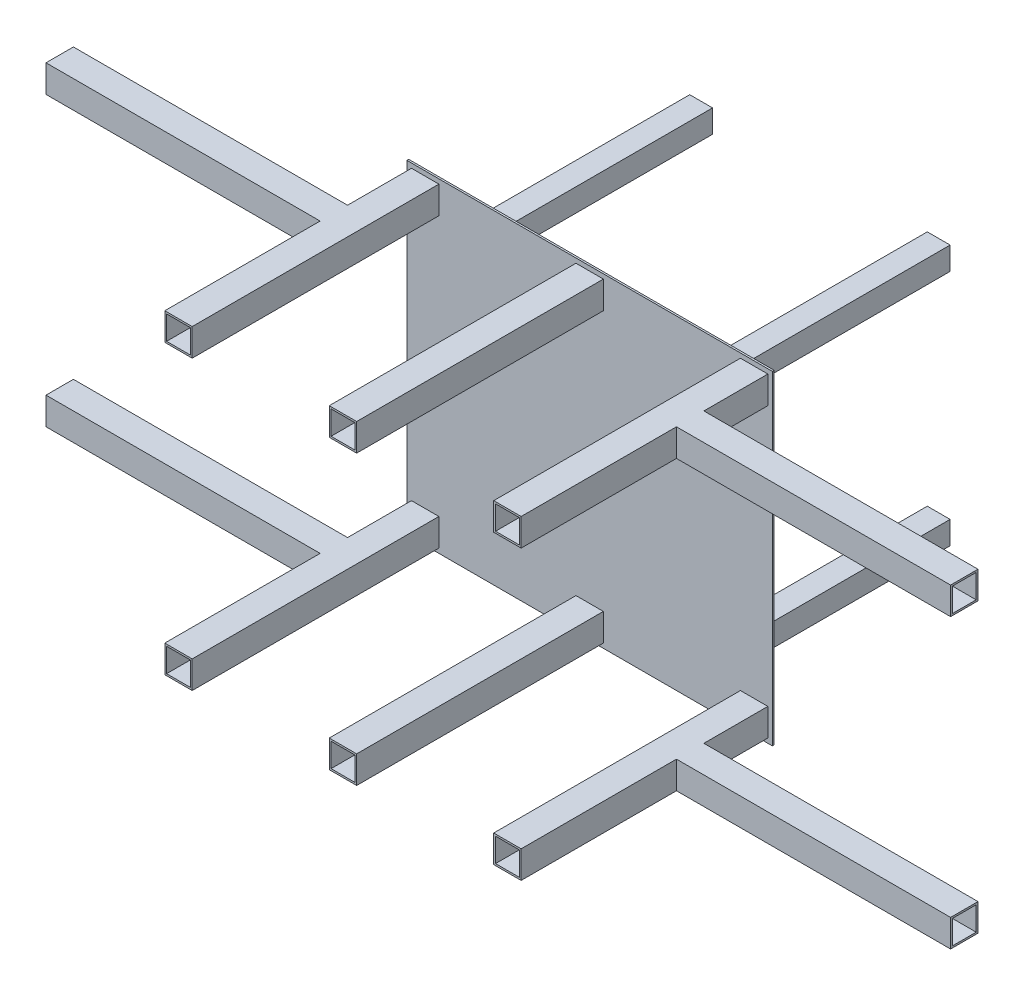
SolidWorks part; units mm, degrees
ref_plane "前基準面" through (0, 0, 0) normal (0, 0, 1) x (1, 0, 0)
ref_plane "上基準面" through (0, 0, 0) normal (0, 1, 0) x (1, 0, 0)
ref_plane "右基準面" through (0, 0, 0) normal (1, 0, 0) x (0, 0, -1)
sketch "草圖1" plane through (0, 0, 0) normal (0, 0, 1) x (1, 0, 0)
  line L0 (27.1343, 30.6601) -> (53.1343, 30.6601)
  line L1 (-159.8657, 37.6601) -> (240.1343, 37.6601)
  line L2 (-159.8657, 37.6601) -> (-159.8657, -317.3399)
  line L3 (-159.8657, -317.3399) -> (240.1343, -317.3399)
  line L4 (240.1343, 37.6601) -> (240.1343, -317.3399)
  line L5 (-152.8657, 30.6601) -> (-126.8657, 30.6601)
  line L6 (-152.8657, 30.6601) -> (-152.8657, 4.6601)
  line L7 (-152.8657, 4.6601) -> (-126.8657, 4.6601)
  line L8 (-126.8657, 30.6601) -> (-126.8657, 4.6601)
  line L9 (-154.8657, 32.6601) -> (-124.8657, 32.6601)
  line L10 (-154.8657, 32.6601) -> (-154.8657, 2.6601)
  line L11 (-154.8657, 2.6601) -> (-124.8657, 2.6601)
  line L12 (-124.8657, 32.6601) -> (-124.8657, 2.6601)
  line L13 (25.1343, 32.6601) -> (55.1343, 32.6601)
  line L14 (25.1343, 32.6601) -> (25.1343, 2.6601)
  line L15 (25.1343, 2.6601) -> (55.1343, 2.6601)
  line L16 (55.1343, 32.6601) -> (55.1343, 2.6601)
  line L17 (53.1343, 30.6601) -> (53.1343, 4.6601)
  line L18 (27.1343, 4.6601) -> (53.1343, 4.6601)
  line L19 (27.1343, 30.6601) -> (27.1343, 4.6601)
  line L20 (207.1343, 4.6601) -> (233.1343, 4.6601)
  line L21 (205.1343, 32.6601) -> (235.1343, 32.6601)
  line L22 (205.1343, 32.6601) -> (205.1343, 2.6601)
  line L23 (205.1343, 2.6601) -> (235.1343, 2.6601)
  line L24 (235.1343, 32.6601) -> (235.1343, 2.6601)
  line L25 (233.1343, 30.6601) -> (233.1343, 4.6601)
  line L26 (207.1343, 30.6601) -> (233.1343, 30.6601)
  line L27 (207.1343, 30.6601) -> (207.1343, 4.6601)
  line L28 (-152.8657, -284.3399) -> (-126.8657, -284.3399)
  line L29 (-154.8657, -282.3399) -> (-124.8657, -282.3399)
  line L30 (-154.8657, -282.3399) -> (-154.8657, -312.3399)
  line L31 (-154.8657, -312.3399) -> (-124.8657, -312.3399)
  line L32 (-124.8657, -282.3399) -> (-124.8657, -312.3399)
  line L33 (25.1343, -282.3399) -> (55.1343, -282.3399)
  line L34 (25.1343, -282.3399) -> (25.1343, -312.3399)
  line L35 (25.1343, -312.3399) -> (55.1343, -312.3399)
  line L36 (55.1343, -282.3399) -> (55.1343, -312.3399)
  line L37 (205.1343, -282.3399) -> (235.1343, -282.3399)
  line L38 (205.1343, -282.3399) -> (205.1343, -312.3399)
  line L39 (205.1343, -312.3399) -> (235.1343, -312.3399)
  line L40 (235.1343, -282.3399) -> (235.1343, -312.3399)
  line L41 (-126.8657, -284.3399) -> (-126.8657, -310.3399)
  line L42 (-152.8657, -310.3399) -> (-126.8657, -310.3399)
  line L43 (-152.8657, -284.3399) -> (-152.8657, -310.3399)
  line L44 (27.1343, -284.3399) -> (53.1343, -284.3399)
  line L45 (53.1343, -284.3399) -> (53.1343, -310.3399)
  line L46 (27.1343, -310.3399) -> (53.1343, -310.3399)
  line L47 (27.1343, -284.3399) -> (27.1343, -310.3399)
  line L48 (207.1343, -284.3399) -> (233.1343, -284.3399)
  line L49 (233.1343, -284.3399) -> (233.1343, -310.3399)
  line L50 (207.1343, -310.3399) -> (233.1343, -310.3399)
  line L51 (207.1343, -284.3399) -> (207.1343, -310.3399)
  point P52 (-139.8657, -312.3399)
  dimension "D1" = 400
  dimension "D2" = 355
  dimension "D3" = 30
  dimension "D4" = 30
  dimension "D5" = 26
  dimension "D6" = 26
  dimension "D7" = 2
  dimension "D8" = 2
  dimension "D9" = 30
  dimension "D10" = 30
  dimension "D12" = 30
  dimension "D13" = 30
  dimension "D15" = 150
  dimension "D16" = 150
  dimension "D17" = 5
  dimension "D18" = 0
  dimension "D19" = 0
  dimension "D20" = 30
  dimension "D21" = 30
  dimension "D23" = 30
  dimension "D24" = 30
  dimension "D26" = 30
  dimension "D27" = 30
  dimension "D29" = 285
  dimension "D30" = 0
  dimension "D31" = 0
  dimension "D32" = 5
  dimension "D33" = 150
  dimension "D34" = 150
  dimension "D35" = 0
  dimension "D11" = 2
  dimension "D14" = 2
  dimension "D22" = 2
  dimension "D25" = 2
  dimension "D28" = 2
extrude "填料-伸長1" add sketch "草圖1" along normal blind 270 contours L32 L31 L30 L29 | L42 L41 L28 L43 | L35 L36 L33 L34 | L46 L45 L44 L47 | L50 L49 L48 L51 | L39 L40 L37 L38 | L23 L24 L21 L22 | L20 L25 L26 L27 | L15 L16 L13 L14 | L18 L17 L0 L19 | L11 L12 L9 L10 | L7 L8 L5 L6
extrude "填料-伸長2" add sketch "草圖1<4>" against normal blind 2 contours L4 L3 L2 L1
sketch "草圖1<4>" plane through (0, 0, 0) normal (0, 0, 1) x (1, 0, 0) same geometry as "草圖1"
sketch "草圖3" plane through (0, 0, -2) normal (0, 0, -1) x (-1, 0, 0)
  line L0 (-181.1343, 1.1601) -> (-159.1343, 1.1601)
  line L1 (-182.6343, 2.6601) -> (-157.6343, 2.6601)
  line L2 (-182.6343, 2.6601) -> (-182.6343, -22.3399)
  line L3 (-182.6343, -22.3399) -> (-157.6343, -22.3399)
  line L4 (-157.6343, 2.6601) -> (-157.6343, -22.3399)
  line L5 (-159.1343, 1.1601) -> (-159.1343, -20.8399)
  line L6 (-181.1343, -20.8399) -> (-159.1343, -20.8399)
  line L7 (-181.1343, 1.1601) -> (-181.1343, -20.8399)
  line L9 (-240.1343, 37.6601) -> (-240.1343, -317.3399) construction
  line L10 (159.8657, 37.6601) -> (-240.1343, 37.6601) construction
  line L11 (-181.1343, -258.8399) -> (-159.1343, -258.8399)
  line L12 (-182.6343, -257.3399) -> (-157.6343, -257.3399)
  line L13 (-182.6343, -257.3399) -> (-182.6343, -282.3399)
  line L14 (-182.6343, -282.3399) -> (-157.6343, -282.3399)
  line L15 (-157.6343, -257.3399) -> (-157.6343, -282.3399)
  line L16 (-159.1343, -258.8399) -> (-159.1343, -280.8399)
  line L17 (-181.1343, -280.8399) -> (-159.1343, -280.8399)
  line L18 (-181.1343, -258.8399) -> (-181.1343, -280.8399)
  line L19 (159.8657, -317.3399) -> (-240.1343, -317.3399) construction
  line L20 (-40.1343, 37.6601) -> (-40.1343, -317.3399) construction
  line L21 (100.8657, -258.8399) -> (100.8657, -280.8399)
  line L22 (100.8657, -280.8399) -> (78.8657, -280.8399)
  line L23 (78.8657, -258.8399) -> (78.8657, -280.8399)
  line L24 (77.3657, -257.3399) -> (77.3657, -282.3399)
  line L25 (102.3657, -282.3399) -> (77.3657, -282.3399)
  line L26 (102.3657, -257.3399) -> (102.3657, -282.3399)
  line L27 (102.3657, -257.3399) -> (77.3657, -257.3399)
  line L28 (100.8657, -258.8399) -> (78.8657, -258.8399)
  line L29 (100.8657, 1.1601) -> (100.8657, -20.8399)
  line L30 (100.8657, -20.8399) -> (78.8657, -20.8399)
  line L31 (78.8657, 1.1601) -> (78.8657, -20.8399)
  line L32 (77.3657, 2.6601) -> (77.3657, -22.3399)
  line L33 (102.3657, -22.3399) -> (77.3657, -22.3399)
  line L34 (102.3657, 2.6601) -> (102.3657, -22.3399)
  line L35 (102.3657, 2.6601) -> (77.3657, 2.6601)
  line L36 (100.8657, 1.1601) -> (78.8657, 1.1601)
  point P12 (-182.6343, -9.8399)
  dimension "D1" = 25
  dimension "D2" = 25
  dimension "D4" = 57.5
  dimension "D5" = 35
  dimension "D6" = 25
  dimension "D7" = 25
  dimension "D9" = 57.5
  dimension "D10" = 35
  dimension "D3" = 1.5
  dimension "D8" = 1.5
extrude "填料-伸長3" add sketch "草圖3" along normal blind 250 contours L12 L15 L14 L13 | L11 L16 L17 L18 | L26 L25 L24 L27 | L21 L22 L23 L28 | L29 L30 L31 L36 | L34 L33 L32 L35 | L4 L3 L2 L1 | L5 L6 L7 L0
sketch "草圖8" plane through (-154.8657, 0, 0) normal (-1, 0, 0) x (0, 0, 1)
  line L0 (270, -312.3399) -> (0, -312.3399) construction
  line L1 (70, -312.3399) -> (100, -312.3399)
  line L2 (70, -312.3399) -> (70, -282.3399)
  line L3 (70, -282.3399) -> (100, -282.3399)
  line L4 (100, -312.3399) -> (100, -282.3399)
  line L5 (270, -282.3399) -> (0, -282.3399) construction
  line L6 (270, -282.3399) -> (270, -312.3399) construction
  line L7 (270, 2.6601) -> (0, 2.6601) construction
  line L8 (70, 2.6601) -> (100, 2.6601)
  line L9 (70, 2.6601) -> (70, 32.6601)
  line L10 (70, 32.6601) -> (100, 32.6601)
  line L11 (100, 2.6601) -> (100, 32.6601)
  line L12 (270, 32.6601) -> (0, 32.6601) construction
  line L14 (72, -310.3399) -> (98, -310.3399)
  line L15 (72, -310.3399) -> (72, -284.3399)
  line L16 (72, -284.3399) -> (98, -284.3399)
  line L17 (98, -310.3399) -> (98, -284.3399)
  line L18 (72, 4.6601) -> (98, 4.6601)
  line L19 (72, 4.6601) -> (72, 30.6601)
  line L20 (72, 30.6601) -> (98, 30.6601)
  line L21 (98, 4.6601) -> (98, 30.6601)
  dimension "D1" = 30
  dimension "D2" = 170
  dimension "D3" = 26
  dimension "D4" = 26
  dimension "D5" = 2
  dimension "D6" = 2
  dimension "D7" = 2
  dimension "D8" = 2
extrude "填料-伸長4" add sketch "草圖8" along normal blind 300
ref_plane "平面1" through (40.1343, 0, 0) normal (-1, 0, 0) x (0, 0, 1)
mirror "鏡射1" about plane through (40.1343, 0, 0) normal (-1, 0, 0) of "填料-伸長4"
